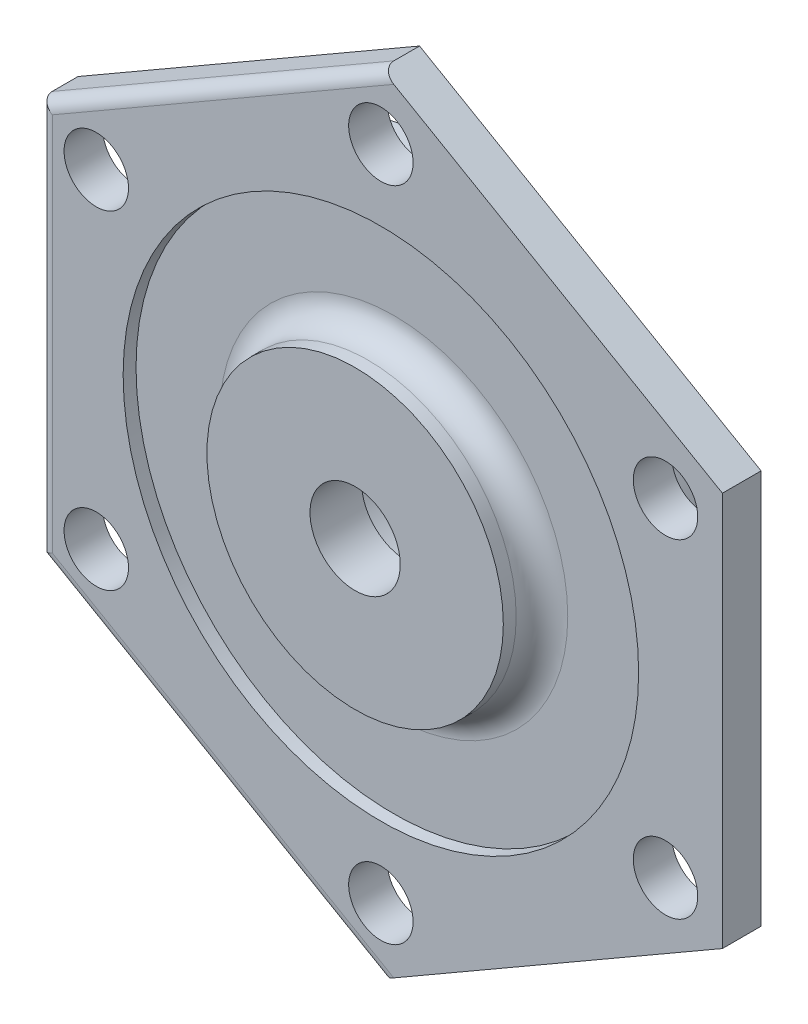
SolidWorks part; units mm, degrees
ref_plane "Front Plane" through (0, 0, 0) normal (0, 0, 1) x (1, 0, 0)
ref_plane "Top Plane" through (0, 0, 0) normal (0, 1, 0) x (1, 0, 0)
ref_plane "Right Plane" through (0, 0, 0) normal (1, 0, 0) x (0, 0, -1)
sketch "Sketch1" plane through (0, 0, 0) normal (0, 0, 1) x (1, 0, 0)
  line L0 (0, 70.9552) -> (0, -70.9552) construction
  line L1 (53, -30.5996) -> (53, 30.5996)
  line L2 (53, 30.5996) -> (0, 61.1991)
  line L3 (0, 61.1991) -> (-53, 30.5996)
  line L4 (-53, 30.5996) -> (-53, -30.5996)
  line L5 (-53, -30.5996) -> (0, -61.1991)
  line L6 (0, -61.1991) -> (53, -30.5996)
  line L7 (0, 0) -> (0, 51) construction
  circle A0 centre (0, 0) radius 53 construction
  circle A1 centre (0, 0) radius 7
  circle A2 centre (0, 0) radius 14
  circle A3 centre (0, 0) radius 19
  circle A4 centre (0, 0) radius 23
  circle A5 centre (0, 0) radius 51 construction
  circle A6 centre (0, 51) radius 5
  circle A7 centre (0, 0) radius 45
  circle A8 centre (0, 0) radius 40
  circle A9 centre (44.1673, 25.5) radius 5
  circle A10 centre (44.1673, -25.5) radius 5
  circle A11 centre (0, -51) radius 5
  circle A12 centre (-44.1673, -25.5) radius 5
  circle A13 centre (-44.1673, 25.5) radius 5
  point P11 (0, 0)
  dimension "D2" = 102
  dimension "D3" = 10
  dimension "D4" = 14
  dimension "D5" = 28
  dimension "D6" = 38
  dimension "D7" = 46
  dimension "D8" = 90
  dimension "D9" = 80
  dimension "D1" = 106
  dimension "D11" = 51
  dimension "D10" = 6
extrude "Boss-Extrude1" add sketch "Sketch1" along normal blind 8 contours A2 A1 region at (-13.604, 0, 0)
extrude "Boss-Extrude2" add sketch "Sketch1<3>" along normal blind 8 contours A3 A2 | A4 A3 region at (-18.4626, 0, 0) region at (-22.3495, 0, 0)
sketch "Sketch1<3>" plane through (0, 0, 0) normal (0, 0, 1) x (1, 0, 0) same geometry as "Sketch1"
extrude "Boss-Extrude3" add sketch "Sketch1<4>" against normal blind 8 contours A3 A2 region at (-18.4626, 0, 0)
sketch "Sketch1<4>" plane through (0, 0, 0) normal (0, 0, 1) x (1, 0, 0) same geometry as "Sketch1"
extrude "Boss-Extrude4" add sketch "Sketch1<5>" along normal blind 2 contours A8 A4 region at (-38.8686, 0, 0)
sketch "Sketch1<5>" plane through (0, 0, 0) normal (0, 0, 1) x (1, 0, 0) same geometry as "Sketch1"
extrude "Boss-Extrude5" add sketch "Sketch1<6>" against normal blind 4 contours A8 A4 region at (-38.8686, 0, 0)
sketch "Sketch1<6>" plane through (0, 0, 0) normal (0, 0, 1) x (1, 0, 0) same geometry as "Sketch1"
extrude "Boss-Extrude6" add sketch "Sketch1<8>" against normal blind 8 contours A7 A8 region at (-43.7272, 0, 0)
sketch "Sketch1<8>" plane through (0, 0, 0) normal (0, 0, 1) x (1, 0, 0) same geometry as "Sketch1"
extrude "Boss-Extrude7" add sketch "Sketch1<9>" along normal blind 4 contours A7 A8 region at (-43.7272, 0, 0)
sketch "Sketch1<9>" plane through (0, 0, 0) normal (0, 0, 1) x (1, 0, 0) same geometry as "Sketch1"
extrude "Boss-Extrude8" add sketch "Sketch1<10>" against normal blind 2 contours L5 L6 L1 L2 L3 L4 A13 A12 A11 A10 A9 A7 A6 region at (25.6904, -44.4971, 0)
sketch "Sketch1<10>" plane through (0, 0, 0) normal (0, 0, 1) x (1, 0, 0) same geometry as "Sketch1"
extrude "Boss-Extrude10" add sketch "Sketch1<12>" along normal blind 4 contours L5 L6 L1 L2 L3 L4 A13 A12 A11 A10 A9 A7 A6 region at (25.6904, -44.4971, 0)
sketch "Sketch1<12>" plane through (0, 0, 0) normal (0, 0, 1) x (1, 0, 0) same geometry as "Sketch1"
fillet "Fillet1" radius 4 1 edges at (23, 0, 2)
chamfer "Chamfer1" distance 1 angle 45 1 edges at (45, 0, -8)
fillet "Fillet2" radius 2 3 edges at (-26.5, 45.8993, 4) (-53, 0, 4) (-26.5, -45.8993, 4)
